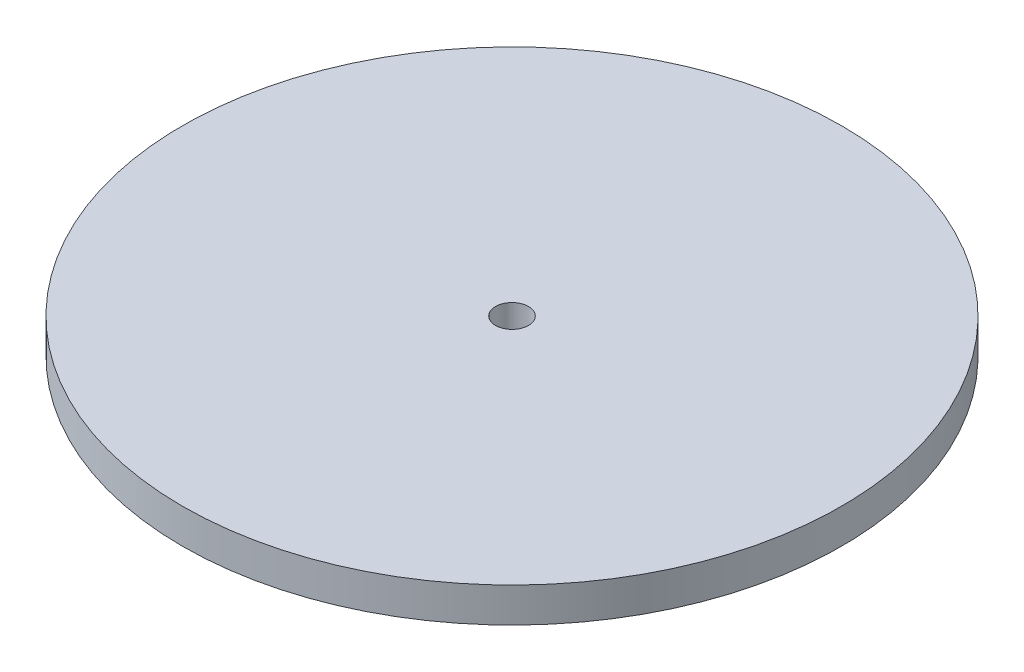
SolidWorks part; units mm, degrees
ref_plane "Front Plane" through (0, 0, 0) normal (0, 0, 1) x (1, 0, 0)
ref_plane "Top Plane" through (0, 0, 0) normal (0, 1, 0) x (1, 0, 0)
ref_plane "Right Plane" through (0, 0, 0) normal (1, 0, 0) x (0, 0, -1)
sketch "Sketch1" plane through (0, 0, 0) normal (0, 1, 0) x (1, 0, 0)
  circle A0 centre (0, 0) radius 19
  dimension "D1" = 38
extrude "Boss-Extrude1" add sketch "Sketch1" along normal blind 2
sketch "Sketch2" plane through (0, 2, 0) normal (0, 1, 0) x (1, 0, 0)
  circle A0 centre (0, 0) radius 0.95
  dimension "D1" = 1.9
extrude "Cut-Extrude1" cut sketch "Sketch2" against normal blind 2
